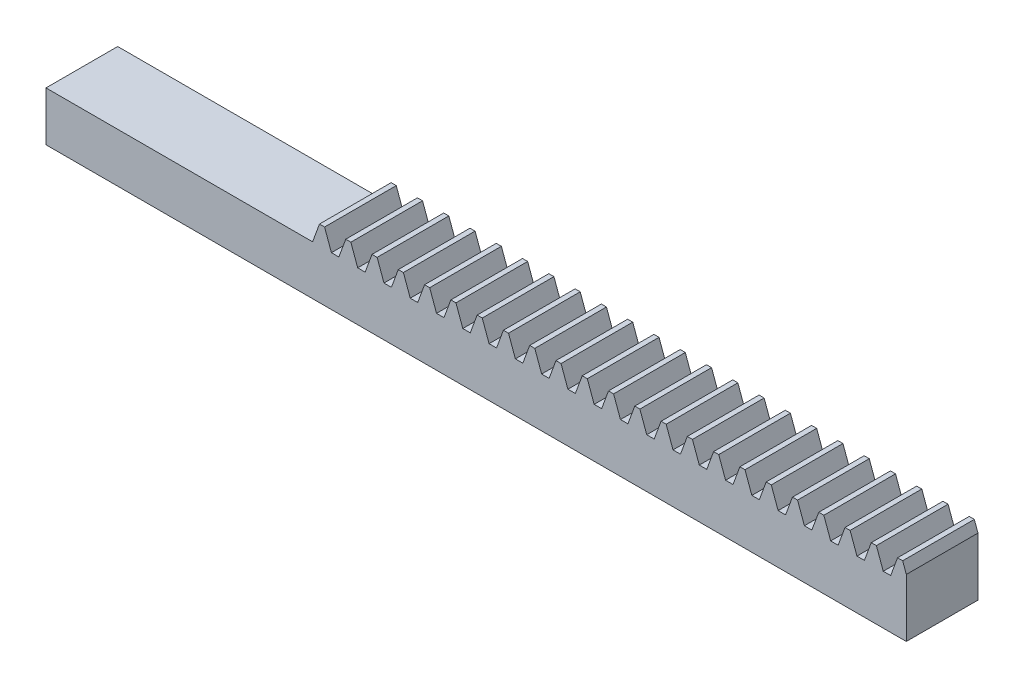
SolidWorks part; units mm, degrees
extrude "Blank" add sketch "BlankSke" against normal blind 6
sketch "BlankSke" plane through (0, 0, 0) normal (0, 0, 1) x (1, 0, 0)
  line L1 (0, 0) -> (50, 0)
  line L2 (0, 0) -> (0, 5.7)
  line L3 (0, 5.7) -> (50, 5.7)
  line L4 (50, 0) -> (50, 5.7)
  dimension "Length" = 50
ref_plane "Plane1" through (0, 0, 0) normal (0, 0, 1) x (1, 0, 0)
ref_plane "Plane2" through (0, 0, 0) normal (0, 1, 0) x (1, 0, 0)
ref_plane "Plane3" through (0, 0, 0) normal (1, 0, 0) x (0, 0, -1)
sketch "HoldingSke" plane through (0, 0, 0) normal (0, 1, 0) x (1, 0, 0)
  line L0 (0, 0) -> (0.1988, 1.4147)
  line L1 (-15, 0) -> (100, 0) construction
  line L2 (0, 0) -> (-2.1039, 2.3779)
  line L3 (0, 0) -> (-11.863, 4.5341)
  line L4 (0, 0) -> (7.8894, 3.5126)
  line L5 (0, 0) -> (-23.7986, -8.8762)
  line L6 (0, 0) -> (-10.5278, -7.1032)
  line L9 (-71.009, 38.7566) -> (-24.0243, 55.8576)
  line L10 (-76.2, 3.0779) -> (-71.2, 3.0779)
  line L11 (0, 0) -> (-6, 0)
  line L12 (-76.2, 101.6) -> (-76.173, 101.6)
  line L13 (24.9733, 27.94) -> (52.9518, 28.4284)
  line L14 (24.9733, 27.94) -> (24.9743, 27.94)
  line L15 (24.9733, 27.94) -> (100.4006, 29.5858)
  circle A0 centre (0, 0) radius 19.05
  circle A1 centre (0, 0) radius 2.5
  circle A2 centre (0, 0) radius 12.7
  dimension "Num_teeth" = 24
  dimension "Width" = 6
  dimension "Length" = 50
  dimension "Pitch_height" = 5
sketch "TooCutSkeIll" plane through (0, 0, 0) normal (0, 0, 1) x (1, 0, 0)
  line L0 (-0.8789, 5.6816) -> (-0.3545, 4.2408)
  line L1 (-0.1891, 4.125) -> (0.1891, 4.125)
  line L2 (0.3545, 4.2408) -> (0.8789, 5.6816)
  line L3 (50, 5.7) -> (0, 5.7) construction
  line L4 (0, 0) -> (0, 64.897) construction
  line L5 (-13.208, 5) -> (12.954, 5) construction
  line L6 (0, 0) -> (50, 0) construction
  line L7 (0.6308, 5) -> (0.6308, 48.7463) construction
  line L8 (-0.6308, 5) -> (-0.6308, 48.7463) construction
  line L9 (0.9052, 5.7) -> (0.9052, 5.7254)
  line L10 (-0.9052, 5.7) -> (-0.9052, 5.7254)
  line L11 (-0.9052, 5.7254) -> (0.9052, 5.7254)
  arc A0 (0.1891, 4.125) -> (0.3545, 4.2408) centre (0.1891, 4.301) ccw
  arc A1 (-0.3545, 4.2408) -> (-0.1891, 4.125) centre (-0.1891, 4.301) ccw
  arc A2 (0.9052, 5.7) -> (0.8789, 5.6816) centre (0.9052, 5.672) ccw
  arc A3 (-0.8789, 5.6816) -> (-0.9052, 5.7) centre (-0.9052, 5.672) ccw
  dimension "Addendum_plus" = 0.7254
  dimension "Pitch_height" = 5
  dimension "Pressure_angle" = 20
  dimension "Gap_width" = 1.2616
  dimension "Dedendum" = 0.875
extrude "ToothCutIll" [suppressed] cut sketch "TooCutSkeIll" against normal through all
sketch "TooCutSkeSim" plane through (0, 0, 0) normal (0, 0, 1) x (1, 0, 0)
  line L0 (0.3123, 4.125) -> (-0.3123, 4.125)
  line L1 (0.8948, 5.7254) -> (0.3123, 4.125)
  line L2 (0, 17.4625) -> (0, 53.467) construction
  line L3 (0.8948, 5.7254) -> (-0.8948, 5.7254)
  line L6 (-0.8948, 5.7254) -> (-0.3123, 4.125)
  line L9 (-0.6308, 5) -> (0.6308, 5) construction
  line L10 (0, 0) -> (50, 0) construction
  line L11 (0.6308, 5) -> (0.6308, 53.467) construction
  line L12 (-0.6308, 5) -> (-0.6308, 53.467) construction
  dimension "Addendum_plus" = 0.7254
  dimension "Pitch_height" = 5
  dimension "Pressure_angle" = 20
  dimension "Gap_width" = 1.2616
  dimension "Dedendum" = 0.875
extrude "ToothCutSim" cut sketch "TooCutSkeSim" against normal through all
pattern_linear "TeethCuts" count 24 spacing 2.1991 along (1, 0, 0) of "ToothCutIll", "ToothCutSim"
sketch "草图1" plane through (0, 0, 0) normal (-1, 0, 0) x (0, 0, 1)
  line L1 (-6, 4.125) -> (0, 4.125)
  line L2 (-6, 4.125) -> (-6, 0)
  line L3 (-6, 0) -> (0, 0)
  line L4 (0, 4.125) -> (0, 0)
extrude "凸台-拉伸1" add sketch "草图1" along normal blind 22
equation "' \"Module@HoldingSke\" = 6.35"
equation "' \"Num_teeth@HoldingSke\" = 12"
equation "' \"Ap@HoldingSke\" =  20"
equation "' \"Ap@HoldingSke\" = 20"
equation "' \"Width@HoldingSke\" = 0.25 * 25.4"
equation "' \"Show_teeth@HoldingSke\" = 500"
equation "' \"Backlash@HoldingSke\" = 0.009 * 25.4"
equation "' \"Addendum_fac@HoldingSke\" = 1.0"
equation "' \"Dedendum_fac@HoldingSke\" = 1.25"
equation "' \"Dedendum_add@HoldingSke\" = 0.00005 * 25.4"
equation "' \"Clearance_fac@HoldingSke\" = 0.25"
equation "' \"Pitch_height@HoldingSke\" = 1 * 25.4"
equation "' \"Length@HoldingSke\" = 4.71 * 25.4"
equation "\"Pitch@HoldingSke\" = 1 / \"Module@HoldingSke\""
equation "\"MPH@HoldingSke\" = \"Dedendum_fac@HoldingSke\" / \"Pitch@HoldingSke\" + 2 * \"Dedendum_add@HoldingSke\" + 0.002 * 25.4"
equation "\"MPH@HoldingSke\" = ((sgn( \"MPH@HoldingSke\" - \"Pitch_height@HoldingSke\")+1)*( \"MPH@HoldingSke\" - \"Pitch_height@HoldingSke\"))/2 + \"Pitch_height@HoldingSke\""
equation "\"Blank_height@BlankSke\" = \"Pitch_height@HoldingSke\" + \"Addendum_fac@HoldingSke\"  / \"Pitch@HoldingSke\" "
equation "\"Length@BlankSke\" =  \"Length@HoldingSke\""
equation "\"Face_width@Blank\" = \"Width@HoldingSke\""
equation "\"Pressure_angle@TooCutSkeIll\" = \"Ap@HoldingSke\""
equation "\"Addendum_plus@TooCutSkeIll\" =  \"Addendum_fac@HoldingSke\"  / \"Pitch@HoldingSke\" + 0.001 *25.4"
equation "\"Dedendum@TooCutSkeIll\" = \"Dedendum_fac@HoldingSke\"  / \"Pitch@HoldingSke\""
equation "\"Pitch_height@TooCutSkeIll\" =  \"MPH@HoldingSke\""
equation "\"Gap_width@TooCutSkeIll\" = 3.14159265 / 2 / \"Pitch@HoldingSke\" + 6 * \"Backlash@HoldingSke\""
equation "\"Pressure_angle@TooCutSkeSim\" = \"Ap@HoldingSke\""
equation "\"Addendum_plus@TooCutSkeSim\" =  \"Addendum_fac@HoldingSke\"  / \"Pitch@HoldingSke\" + 0.001 * 25.4"
equation "\"Dedendum@TooCutSkeSim\" = \"Dedendum_fac@HoldingSke\"  / \"Pitch@HoldingSke\""
equation "\"Pitch_height@TooCutSkeSim\" =  \"MPH@HoldingSke\""
equation "\"Gap_width@TooCutSkeSim\" = 3.14159265 / 2 / \"Pitch@HoldingSke\" + 6 * \"Backlash@HoldingSke\""
equation "\"Root_fillet@TooCutSkeIll\" = \"Clearance_fac@HoldingSke\" / \"Pitch@HoldingSke\" + \"Dedendum_add@HoldingSke\""
equation "\"Break_rad@TooCutSkeIll\" = 0.02 / \"Pitch@HoldingSke\" * 2"
equation "\"Linear_pitch@TeethCuts\" = 3.14159265 / \"Pitch@HoldingSke\""
equation "\"Num_teeth@HoldingSke\" = int( ( \"Length@HoldingSke\" + 0 ) / (3.14159265 / \"Pitch@HoldingSke\")) + 0.9999  + 1"
equation " \"Num_teeth@TeethCuts\" = int( \"Show_teeth@HoldingSke\" ) + 1"
equation " \"Num_teeth@TeethCuts\" = ((sgn( \"Num_teeth@TeethCuts\" - \"Num_teeth@HoldingSke\" )-1)*( \"Num_teeth@TeethCuts\" - \"Num_teeth@HoldingSke\" ))/-2+ \"Num_teeth@HoldingSke\""
equation " \"Num_teeth@TeethCuts\" = ((sgn( \"Num_teeth@TeethCuts\" - 2.0)+1)*( \"Num_teeth@TeethCuts\" - 2.0))/2 +2.0"
